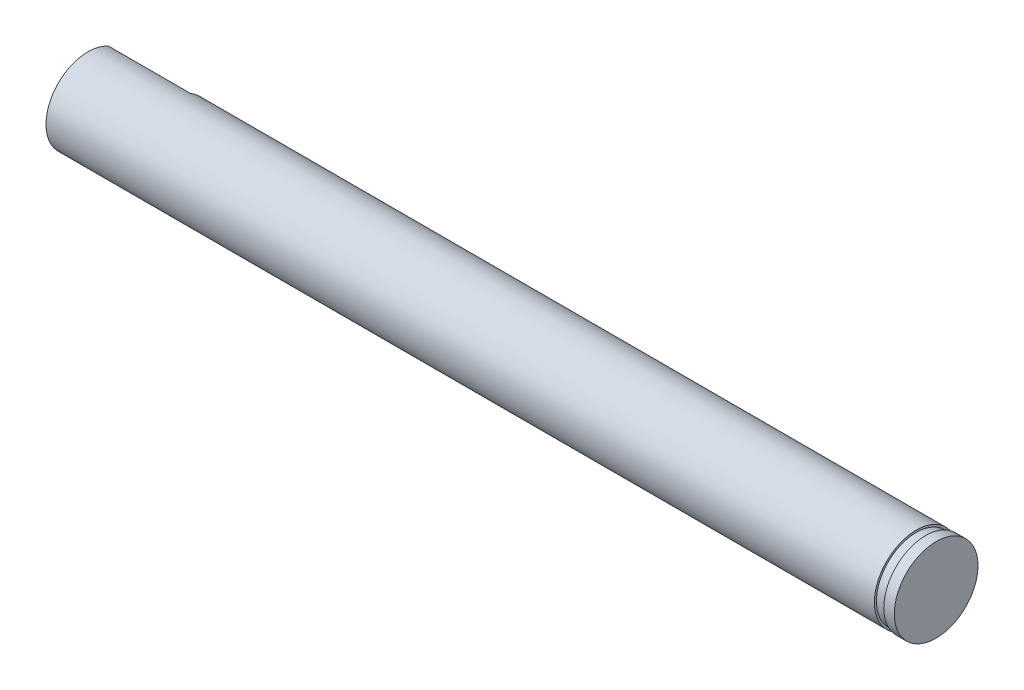
SolidWorks part; units mm, degrees
ref_plane "Front Plane" through (0, 0, 0) normal (0, 0, 1) x (1, 0, 0)
ref_plane "Top Plane" through (0, 0, 0) normal (0, 1, 0) x (1, 0, 0)
ref_plane "Right Plane" through (0, 0, 0) normal (1, 0, 0) x (0, 0, -1)
sketch "Sketch1" plane through (0, 0, 0) normal (1, 0, 0) x (0, 0, -1)
  line L0 (1.985, 3.467) -> (1.985, -3.467)
  line L1 (-3.995, -8) -> (1.985, -8) construction
  line L2 (-3.995, -8) -> (-3.995, 0) construction
  line L4 (1.985, -8) -> (1.985, 3.467) construction
  arc A0 (1.985, 3.467) -> (1.985, -3.467) centre (0, 0) ccw
  dimension "D1" = 7.99
  dimension "D2" = 5.98
  dimension "D3" = 8
extrude "Boss-Extrude1" add sketch "Sketch1" along normal blind 7.8
sketch "Sketch2" plane through (7.8, 0, 0) normal (1, 0, 0) x (0, 0, -1)
  circle A0 centre (0, 0) radius 3.995
  dimension "D1" = 7.99
extrude "Boss-Extrude2" add sketch "Sketch2" along normal blind 73.146
sketch "Sketch3" plane through (80.946, 0, 0) normal (1, 0, 0) x (0, 0, -1)
  circle A0 centre (0, 0) radius 3.8
  circle A1 centre (0, 0) radius 5
  dimension "D1" = 7.6
  dimension "D2" = 10
extrude "Cut-Extrude1" cut sketch "Sketch3" against normal blind 0.9 from offset 1 offset against normal yes
ref_plane "Plane1" through (0, 0, -3.995) normal (0, 0, -1) x (-1, 0, 0)
sketch "Sketch4" plane through (0, 0, -3.995) normal (0, 0, -1) x (-1, 0, 0)
  line L0 (0, 0) -> (-43.434, 0) construction
  circle A0 centre (-43.434, 0) radius 1.778
  dimension "D2" = 3.556
  dimension "D1" = 43.434
extrude "Cut-Extrude2" cut sketch "Sketch4" against normal blind 1.905 draft 45
